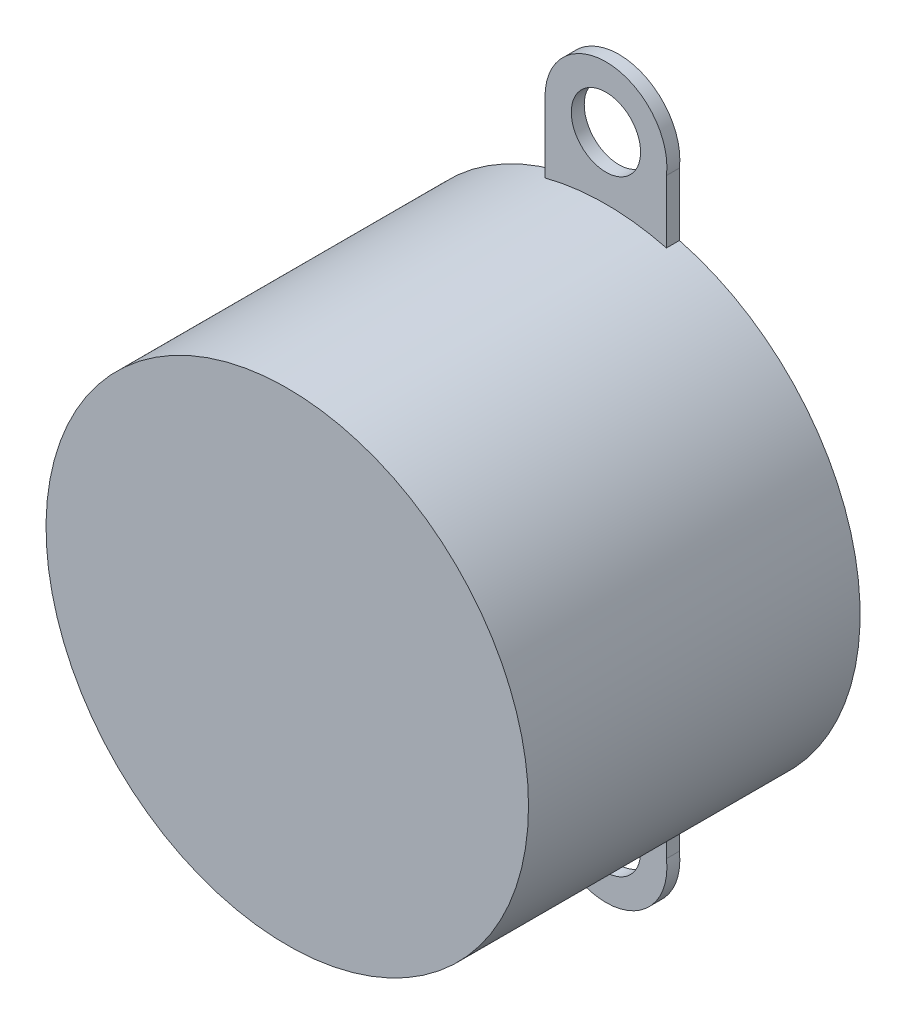
SolidWorks part; units mm, degrees
ref_plane "Front Plane" through (0, 0, 0) normal (0, 0, 1) x (1, 0, 0)
ref_plane "Top Plane" through (0, 0, 0) normal (0, 1, 0) x (1, 0, 0)
ref_plane "Right Plane" through (0, 0, 0) normal (1, 0, 0) x (0, 0, -1)
sketch "Sketch1" plane through (0, 0, 0) normal (0, 0, 1) x (1, 0, 0)
  line L0 (-3.5306, 17.5768) -> (-3.5306, -17.526)
  line L1 (3.5052, 17.5514) -> (3.5052, -17.5514)
  circle A0 centre (0, 0) radius 13.97
  circle A1 centre (0, 17.5768) radius 3.5306
  circle A2 centre (0, -17.526) radius 3.5306
  circle A3 centre (0, 17.5768) radius 2.0066
  circle A4 centre (0, -17.526) radius 2.0066
  dimension "D1" = 27.94
  dimension "D8" = 4.0132
  dimension "D9" = 4.0132
  dimension "D2" = 7.0358
  dimension "D3" = 3.5052
  dimension "D4" = 35.1028
  dimension "D5" = 35.1028
  dimension "D6" = 17.5514
  dimension "D7" = 17.5768
extrude "Boss-Extrude1" add sketch "Sketch1" along normal blind 19.2024 contours L0 A0 | L1 A0 L0 | L1 A0 region at (-0.0124, 0, 0) region at (-7.8779, 0, 0) region at (7.8636, 0, 0)
extrude "Boss-Extrude2" add sketch "Sketch1<3>" along normal blind 0.7493 contours A1 A3 | A1 L0 A0 L1 | A2 L1 A0 L0 | A2 A4 region at (-0.2166, 13.9715, 0) region at (0, 21.0075, 0) region at (-0.0131, -13.9781, 0) region at (-0.2058, -14.1014, 0)
sketch "Sketch1<3>" plane through (0, 0, 0) normal (0, 0, 1) x (1, 0, 0) same geometry as "Sketch1"
sketch "Sketch2" plane through (0, 0, 0) normal (0, 0, 1) x (1, 0, 0)
  circle A0 centre (-7.7468, 0.0508) radius 4.5212
  circle A2 centre (0, 17.5768) radius 2.0066 construction
  dimension "D1" = 9.0424
  dimension "D2" = 7.747
  dimension "D3" = 17.526
extrude "Boss-Extrude3" add sketch "Sketch2" against normal blind 1.5748
sketch "Sketch3" plane through (0, 0, -1.5748) normal (0, 0, -1) x (-1, 0, 0)
  circle A0 centre (7.7468, 0.0508) radius 2.4511
  dimension "D1" = 4.9022
extrude "Boss-Extrude4" add sketch "Sketch3" along normal blind 8.3312
